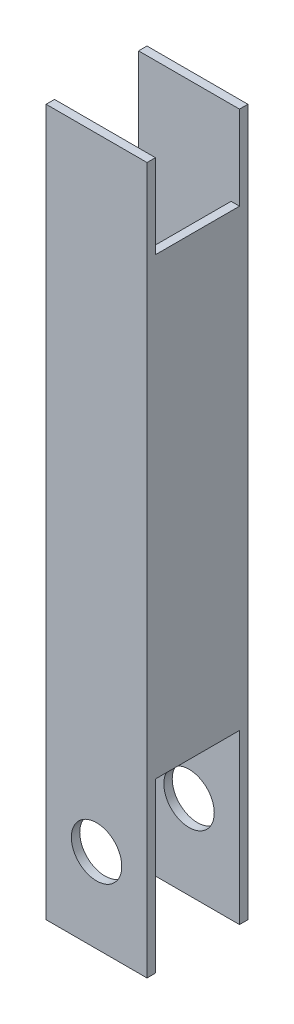
SolidWorks part; units mm, degrees
material "1060 Alloy"
ref_plane "Front Plane" through (0, 0, 0) normal (1, 0, 0) x (0, 1, 0)
ref_plane "Top Plane" through (0, 0, 0) normal (0, 0, 1) x (0, 1, 0)
ref_plane "Right Plane" through (0, 0, 0) normal (0, 1, 0) x (-1, 0, 0)
sketch "Sketch2" plane through (0, 0, 0) normal (0, 1, 0) x (-1, 0, 0)
  line L1 (-30, 30) -> (30, 30)
  line L2 (-30, 30) -> (-30, -30)
  line L3 (-30, -30) -> (30, -30)
  line L4 (30, 30) -> (30, -30)
  line L5 (-30, 30) -> (30, -30) construction
  line L6 (-30, -30) -> (30, 30) construction
  point P0 (0, 0)
  dimension "D1" = 60
  dimension "D2" = 60
extrude "Boss-Extrude1" add sketch "Sketch2" along normal blind 420
shell "Shell1" thickness 5 removed face at (0, 0, 0) removed face at (0, 420, 0)
sketch "Sketch3" plane through (30, 0, 0) normal (1, 0, 0) x (0, 1, 0)
  line L0 (-1000, 0) -> (49000, 0) construction
  line L1 (0, 25) -> (100, 25)
  line L2 (0, 25) -> (0, -25)
  line L3 (0, -25) -> (100, -25)
  line L4 (100, 25) -> (100, -25)
  line L5 (420, 30) -> (0, 30) construction
  line L6 (0, 30) -> (0, -30) construction
  line L7 (420, 30) -> (420, -30) construction
  line L8 (370, 25) -> (420, 25)
  line L9 (370, 25) -> (370, -25)
  line L10 (370, -25) -> (420, -25)
  line L11 (420, 25) -> (420, -25)
  point P7 (0, 0)
  dimension "D1" = 5
  dimension "D2" = 100
  dimension "D3" = 5
  dimension "D4" = 50
extrude "Cut-Extrude1" cut sketch "Sketch3" against normal through all
sketch "Sketch4" plane through (0, 0, 25) normal (0, 0, -1) x (1, 0, 0)
  line L0 (-30, 0) -> (30, -100) construction
  line L1 (30, 0) -> (-30, -100) construction
  line L26 (25, -100) -> (30, -100)
  line L27 (25, -100) -> (30, -100)
  line L28 (25, -370) -> (25, -100)
  line L29 (30, -100) -> (30, 0)
  line L30 (30, -100) -> (30, 0)
  line L31 (-30, 0) -> (-30, -100)
  line L32 (-30, 0) -> (-30, -100)
  line L33 (-30, -100) -> (-25, -100)
  line L34 (-30, -100) -> (-25, -100)
  line L35 (-25, -370) -> (-30, -370)
  line L36 (-25, -370) -> (-30, -370)
  line L37 (-30, -370) -> (-30, -420)
  line L38 (30, -420) -> (30, -370)
  line L39 (30, 0) -> (-30, 0)
  line L40 (30, -370) -> (25, -370)
  line L42 (-25, -100) -> (-25, -370)
  line L45 (-30, -420) -> (30, -420)
  line L51 (30, 0) -> (-30, 0)
  circle A0 centre (0, -50) radius 15
  dimension "D2" = 0
  dimension "D1" = 30
extrude "Cut-Extrude3" cut sketch "Sketch4" against normal through all both and the other way through all contours A0 region at (0, 50, 25)
